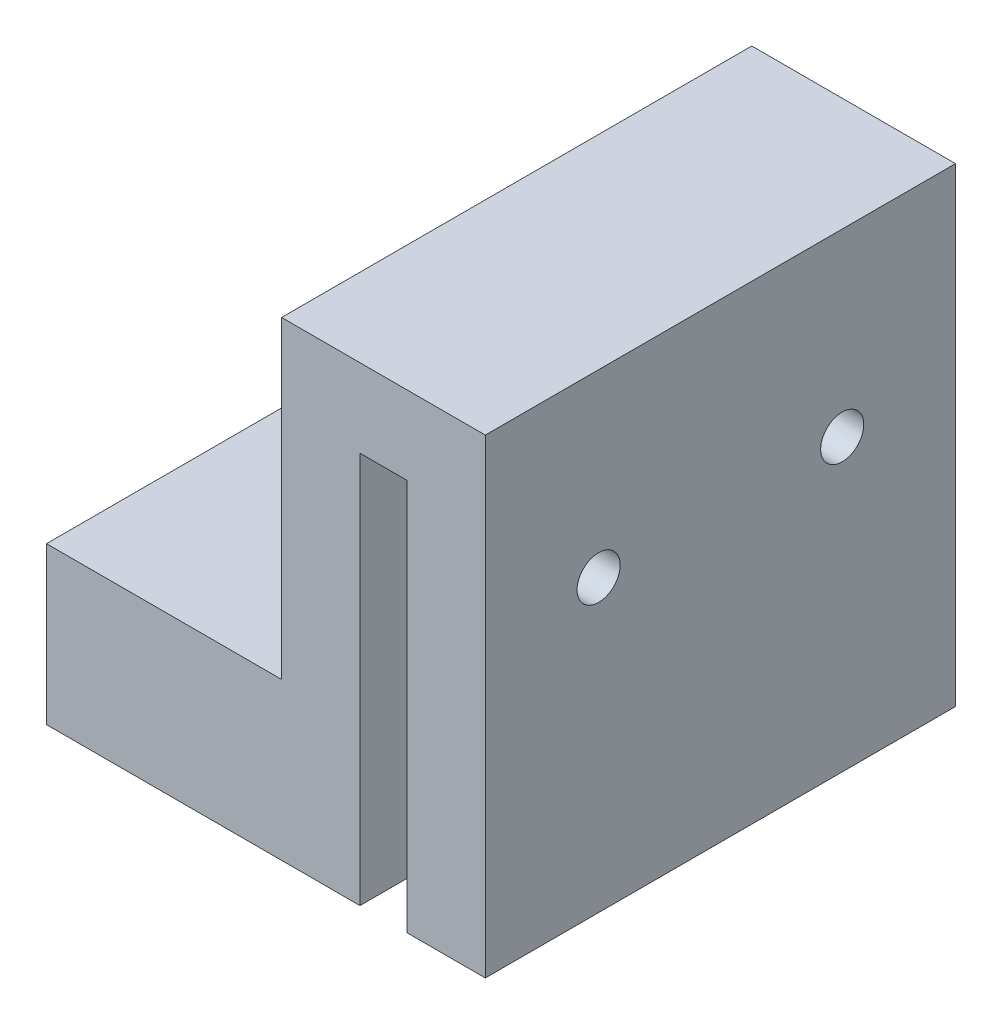
SolidWorks part; units mm, degrees
ref_plane "Front Plane" through (0, 0, 0) normal (0, 0, 1) x (1, 0, 0)
ref_plane "Top Plane" through (0, 0, 0) normal (0, 1, 0) x (1, 0, 0)
ref_plane "Right Plane" through (0, 0, 0) normal (1, 0, 0) x (0, 0, -1)
sketch "Sketch1" plane through (0, 0, 0) normal (0, 0, 1) x (1, 0, 0)
  line L0 (0, 0) -> (0, 60)
  line L1 (0, 60) -> (-26, 60)
  line L2 (-26, 60) -> (-26, 20)
  line L3 (-26, 20) -> (-56, 20)
  line L4 (-56, 20) -> (-56, 0)
  line L5 (-56, 0) -> (-16, 0)
  line L6 (-10, 0) -> (0, 0)
  line L8 (-10, 0) -> (-10, 50)
  line L9 (-10, 50) -> (-16, 50)
  line L10 (-16, 0) -> (-16, 50)
  dimension "D1" = 60
  dimension "D2" = 10
  dimension "30" = 40
  dimension "D3" = 6
  dimension "D4" = 10
  dimension "D5" = 30
  dimension "D6" = 10
extrude "Boss-Extrude1" add sketch "Sketch1" along normal blind 60
sketch "Sketch3" plane through (0, 20, 0) normal (0, 1, 0) x (1, 0, 0)
  line L1 (-31, -25.125) -> (-39.4437, -20.25)
  line L2 (-39.4437, -20.25) -> (-47.8875, -25.125)
  line L3 (-47.8875, -25.125) -> (-47.8875, -34.875)
  line L4 (-47.8875, -34.875) -> (-39.4437, -39.75)
  line L5 (-39.4437, -39.75) -> (-31, -34.875)
  line L6 (-31, -34.875) -> (-31, -25.125)
  line L8 (-26, -60) -> (-26, 0) construction
  circle A1 centre (-39.4437, -30) radius 8.4437 construction
  circle A2 centre (-39.4437, -30) radius 6
  point P14 (-26, -30)
  dimension "D1" = 19.5
  dimension "D2" = 12
  dimension "D3" = 5
extrude "Cut-Extrude1" cut sketch "Sketch3" against normal blind 24 contours A2 region at (-39.4437, 20, 30)
extrude "Cut-Extrude2" cut sketch "Sketch3<3>" along normal blind 8 from surface starting at face at (-39.4437, 0, 36)
sketch "Sketch3<3>" plane through (0, 20, 0) normal (0, 1, 0) x (1, 0, 0) same geometry as "Sketch3"
sketch "Sketch4" plane through (-26, 0, 0) normal (-1, 0, 0) x (0, 0, 1)
  line L0 (14.4586, 37.0312) -> (45.5414, 37.0312) construction
  line L1 (60, 60) -> (0, 60) construction
  circle A0 centre (14.4586, 37.0312) radius 2.75
  circle A1 centre (45.5414, 37.0312) radius 2.75
  point P6 (30, 60)
  point P7 (30, 37.0312)
  dimension "D1" = 5.5
extrude "Cut-Extrude3" cut sketch "Sketch4" against normal blind 30
